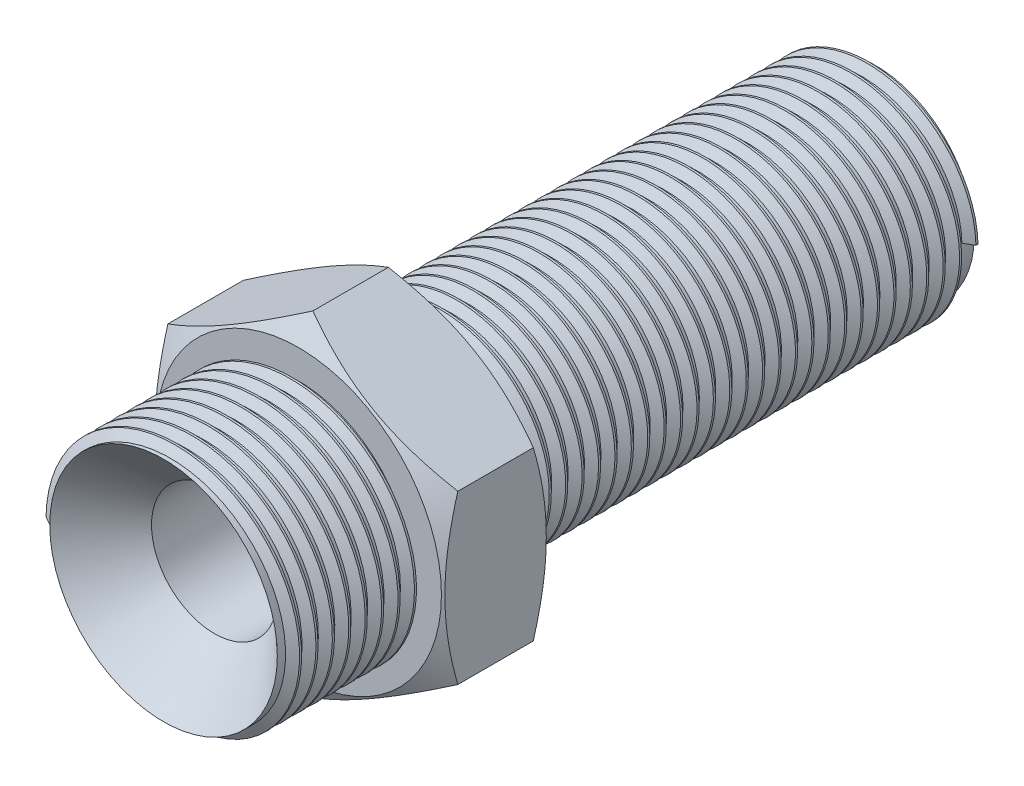
SolidWorks part; units mm, degrees
material "AISI 304"
ref_plane "Ön Düzlem" through (0, 0, 0) normal (0, 0, 1) x (1, 0, 0)
ref_plane "Üst Düzlem" through (0, 0, 0) normal (0, 1, 0) x (1, 0, 0)
ref_plane "Sağ Düzlem" through (0, 0, 0) normal (1, 0, 0) x (0, 0, -1)
sketch "Çizim1" plane through (0, 0, 0) normal (0, 0, 1) x (1, 0, 0)
  line L1 (0, -15.2998) -> (13.25, -7.6499)
  line L2 (13.25, -7.6499) -> (13.25, 7.6499)
  line L3 (13.25, 7.6499) -> (0, 15.2998)
  line L4 (0, 15.2998) -> (-13.25, 7.6499)
  line L5 (-13.25, 7.6499) -> (-13.25, -7.6499)
  line L6 (-13.25, -7.6499) -> (0, -15.2998)
  circle A0 centre (0, 0) radius 13.25 construction
  dimension "D1" = 26.5
extrude "Yükseklik-Ekstrüzyon1" add sketch "Çizim1" along normal blind 9.5
sketch "Çizim2" plane through (0, 0, 9.5) normal (0, 0, 1) x (1, 0, 0)
  circle A0 centre (0, 0) radius 10.4
  dimension "D1" = 20.8
extrude "Yükseklik-Ekstrüzyon3" add sketch "Çizim2" along normal blind 14.5
sketch "Çizim4" plane through (0, 0, 0) normal (0, 0, -1) x (-1, 0, 0)
  circle A0 centre (0, 0) radius 9
  dimension "D1" = 18
extrude "Yükseklik-Ekstrüzyon5" add sketch "Çizim4" along normal blind 45
sketch "Çizim12" plane through (0, 0, 24) normal (0, 0, 1) x (1, 0, 0)
  circle A0 centre (0, 0) radius 5.75
  dimension "D1" = 11.5
extrude "Kes-Ekstrüzyon1" cut sketch "Çizim12" against normal blind 100
chamfer "Pah2" distance 6.8 angle 45 1 edges at (5.75, 0, 24)
chamfer "Pah3" distance 5 angle 45 1 edges at (-5.75, 0, -45)
thread "Diş3" pitch 1.5 start angle 0, offset 0, length 12, pitch 1.5, diameter 20.8
ref_plane "Düzlem11" through (-10.4, 0, 21.85) normal (0, -1, 0) x (-1, 0, 0)
sketch "Diş Profili11" plane through (-10.4, 0, 21.85) normal (0, -1, 0) x (-1, 0, 0)
  line L0 (0, 0) -> (0, 1.5) construction
  line L1 (0, 0) -> (0.8119, 0.4687)
  line L2 (0.8119, 0.4687) -> (0.8119, 0.6562)
  line L3 (0.8119, 0.6562) -> (0, 1.125)
  line L4 (0.8119, 0.5625) -> (0, 0.5625) construction
  line L11 (0, 0) -> (0, 1.125)
  point P2 (0, 0)
  dimension "Pitch" = 1.5
  dimension "Profile_Angle" = 60
  dimension "Profile_Land" = 0.1875
  dimension "Profile_Height" = 0.8119
thread "Diş4" pitch 1.5 start angle 0, offset 0, length 43, pitch 1.5, diameter 18
ref_plane "Düzlem12" through (9, 0, -43.25) normal (0, -1, 0) x (1, 0, 0)
sketch "Diş Profili12" plane through (9, 0, -43.25) normal (0, -1, 0) x (1, 0, 0)
  line L0 (0, 0) -> (0, 1.5) construction
  line L1 (0, 0) -> (0.8119, 0.4687)
  line L2 (0.8119, 0.4687) -> (0.8119, 0.6562)
  line L3 (0.8119, 0.6562) -> (0, 1.125)
  line L4 (0.8119, 0.5625) -> (0, 0.5625) construction
  line L11 (0, 0) -> (0, 1.125)
  point P2 (0, 0)
  dimension "Pitch" = 1.5
  dimension "Profile_Angle" = 60
  dimension "Profile_Land" = 0.1875
  dimension "Profile_Height" = 0.8119
sketch "Sketch1" plane through (0, 0, 0) normal (1, 0, 0) x (0, 0, -1)
  line L2 (-9.5, 15.2998) -> (-9.5, 13.0498)
  line L3 (-9.5, 15.2998) -> (-8.2, 15.2998)
  line L4 (-9.5, 15.2998) -> (0, 15.2998) construction
  line L5 (-8.2, 15.2998) -> (-9.5, 13.0498)
  line L6 (-25.6943, 0) -> (46.1886, 0) construction
  line L7 (0, 15.2998) -> (-1.3, 15.2998)
  line L8 (-1.3, 15.2998) -> (0, 13.0498)
  line L9 (0, 7.6499) -> (0, 15.2998) construction
  line L10 (0, 13.0498) -> (0, 15.2998)
  dimension "D1" = 2.25
  dimension "D2" = 1.3
  dimension "D3" = 1.3
  dimension "D4" = 2.25
revolve "Cut-Revolve1" cut sketch "Sketch1" angle 360 about L6
